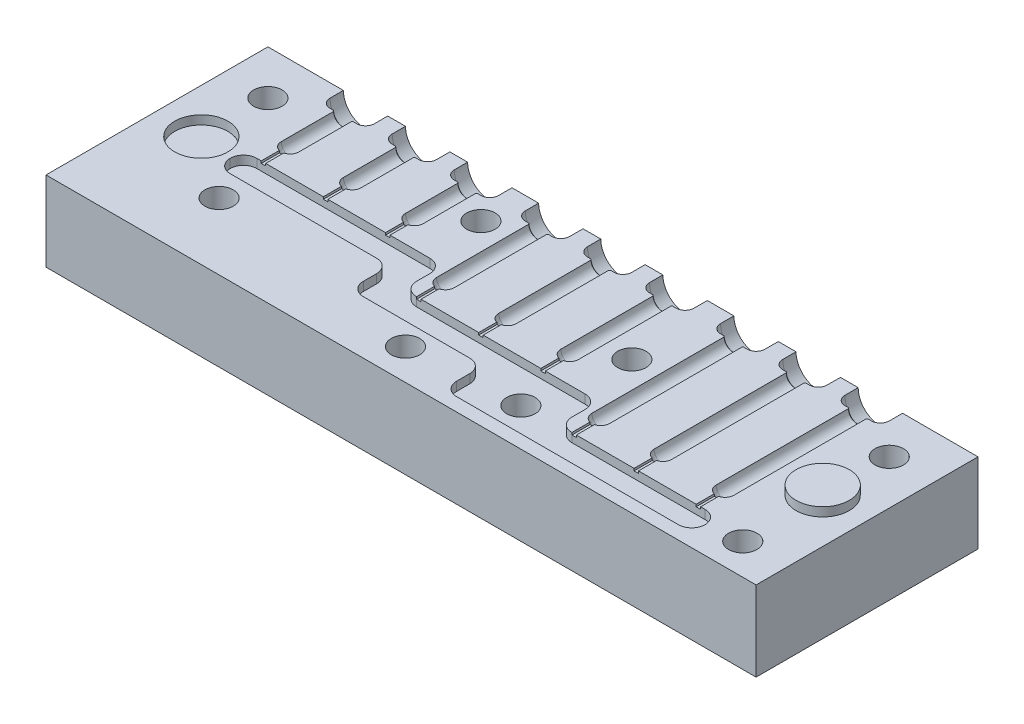
SolidWorks part; units mm, degrees
ref_plane "Ebene vorne" through (0, 0, 0) normal (0, 0, 1) x (1, 0, 0)
ref_plane "Ebene oben" through (0, 0, 0) normal (0, 1, 0) x (1, 0, 0)
ref_plane "Ebene rechts" through (0, 0, 0) normal (1, 0, 0) x (0, 0, -1)
sketch "Skizze1" plane through (0, 0, 0) normal (0, 1, 0) x (1, 0, 0)
  line L1 (0, 0) -> (80, 0)
  line L2 (0, 0) -> (0, 25)
  line L3 (0, 25) -> (80, 25)
  line L4 (80, 0) -> (80, 25)
  dimension "D1" = 80
  dimension "D2" = 25
extrude "Aufsatz-Linear austragen1" add sketch "Skizze1" along normal blind 9
sketch "Skizze2" plane through (0, 0, -25) normal (0, 0, -1) x (-1, 0, 0)
  line L0 (-80, 9) -> (0, 9) construction
  line L1 (-11, 9) -> (-18, 9) construction
  line L2 (-18, 9) -> (-25, 9) construction
  line L3 (-33, 9) -> (-40, 9) construction
  line L4 (-40, 9) -> (-47, 9) construction
  line L5 (-55, 9) -> (-62, 9) construction
  line L6 (-62, 9) -> (-69, 9) construction
  circle A0 centre (-11, 9) radius 1
  circle A1 centre (-18, 9) radius 1
  circle A2 centre (-25, 9) radius 1
  circle A3 centre (-33, 9) radius 1
  circle A4 centre (-40, 9) radius 1
  circle A5 centre (-47, 9) radius 1
  circle A6 centre (-55, 9) radius 1
  circle A7 centre (-62, 9) radius 1
  circle A8 centre (-69, 9) radius 1
  dimension "D1" = 2
  dimension "D2" = 7
  dimension "D3" = 11
  dimension "D5" = 8
  dimension "D4" = 3
extrude "Schnitt-Linear austragen1" cut sketch "Skizze2" against normal blind 9.5 contours A0 | A1 | A2
extrude "Schnitt-Linear austragen2" cut sketch "Skizze2<4>" against normal blind 14 contours A3 | A4 | A5
sketch "Skizze2<4>" plane through (0, 0, -25) normal (0, 0, -1) x (-1, 0, 0) same geometry as "Skizze2"
extrude "Schnitt-Linear austragen3" cut sketch "Skizze2<5>" against normal blind 18.5 contours A6 | A7 | A8
sketch "Skizze2<5>" plane through (0, 0, -25) normal (0, 0, -1) x (-1, 0, 0) same geometry as "Skizze2"
sketch "Skizze4" plane through (0, 0, -25) normal (0, 0, -1) x (-1, 0, 0)
  circle A0 centre (-11, 9) radius 2.5
  circle A1 centre (-18, 9) radius 2.5
  circle A2 centre (-25, 9) radius 2.5
  arc A3 (-12, 9) -> (-10, 9) centre (-11, 9) ccw construction
  arc A4 (-19, 9) -> (-17, 9) centre (-18, 9) ccw construction
  arc A5 (-26, 9) -> (-24, 9) centre (-25, 9) ccw construction
  circle A6 centre (-33, 9) radius 2.5
  circle A7 centre (-40, 9) radius 2.5
  circle A8 centre (-47, 9) radius 2.5
  circle A9 centre (-55, 9) radius 2.5
  circle A10 centre (-62, 9) radius 2.5
  circle A11 centre (-69, 9) radius 2.5
  dimension "D1" = 5
  dimension "D2" = 3
extrude "Schnitt-Linear austragen4" cut sketch "Skizze4" against normal blind 2.5
fillet "Verrundung1" radius 1 18 edges at (69, 6.5, -22.5) (62, 6.5, -22.5) (55, 6.5, -22.5) (47, 6.5, -22.5) (40, 6.5, -22.5) (33, 6.5, -22.5) (25, 6.5, -22.5) (18, 6.5, -22.5) (11, 6.5, -22.5) (11, 8, -15.5) (18, 8, -15.5) (25, 8, -15.5) (33, 8, -11) (40, 8, -11) (47, 8, -11) (55, 8, -6.5) (62, 8, -6.5) (69, 8, -6.5)
chamfer "Fase1" distance 0.1 angle 45 9 edges at (18, 8, -22.5) (11, 8, -22.5) (25, 8, -22.5) (47, 8, -22.5) (40, 8, -22.5) (33, 8, -22.5) (55, 8, -22.5) (62, 8, -22.5) (69, 8, -22.5)
sketch "Skizze5" plane through (0, 9, 0) normal (0, 1, 0) x (1, 0, 0)
  line L0 (11, 15.5) -> (11, 13.5) construction
  line L1 (33, 11) -> (33, 9) construction
  line L2 (10.75, 13.5) -> (11, 13.5)
  line L3 (10.75, 16.5) -> (10.75, 13.5)
  line L4 (11.25, 13.5) -> (11, 13.5)
  line L5 (32.75, 9) -> (33, 9)
  line L6 (32.75, 12) -> (32.75, 9)
  line L7 (33, 9) -> (33.25, 9)
  line L8 (10.75, 16.5) -> (11.25, 16.5)
  line L9 (55, 6.5) -> (55, 4.5) construction
  line L10 (17.75, 13.5) -> (18, 13.5)
  line L11 (33.25, 11) -> (33.25, 9) construction
  line L12 (32.75, 11) -> (32.75, 9) construction
  line L13 (32.75, 12) -> (33.25, 12)
  line L14 (54.75, 4.5) -> (55, 4.5)
  line L15 (54.75, 7.5) -> (54.75, 4.5)
  line L16 (55, 4.5) -> (55.25, 4.5)
  line L17 (54.75, 6.5) -> (54.75, 4.5) construction
  line L18 (11.25, 16.5) -> (11.25, 13.5)
  line L19 (33.25, 12) -> (33.25, 9)
  line L20 (17.75, 16.5) -> (17.75, 13.5)
  line L21 (18.25, 13.5) -> (18, 13.5)
  line L22 (55.25, 6.5) -> (55.25, 4.5) construction
  line L23 (54.75, 7.5) -> (55.25, 7.5)
  line L24 (55.25, 7.5) -> (55.25, 4.5)
  line L25 (39.75, 9) -> (40, 9)
  line L26 (39.75, 12) -> (39.75, 9)
  line L27 (11.25, 15.5) -> (11.25, 13.5) construction
  line L28 (10.75, 15.5) -> (10.75, 13.5) construction
  line L29 (17.75, 16.5) -> (18.25, 16.5)
  line L30 (18.25, 16.5) -> (18.25, 13.5)
  line L31 (18, 15.5) -> (18, 13.5) construction
  line L32 (24.75, 13.5) -> (25, 13.5)
  line L33 (24.75, 16.5) -> (24.75, 13.5)
  line L34 (25.25, 13.5) -> (25, 13.5)
  line L35 (24.75, 16.5) -> (25.25, 16.5)
  line L36 (25.25, 16.5) -> (25.25, 13.5)
  line L37 (25, 15.5) -> (25, 13.5) construction
  line L38 (40, 9) -> (40.25, 9)
  line L39 (39.75, 12) -> (40.25, 12)
  line L40 (40.25, 12) -> (40.25, 9)
  line L41 (40, 11) -> (40, 9) construction
  line L42 (46.75, 9) -> (47, 9)
  line L43 (46.75, 12) -> (46.75, 9)
  line L44 (47, 9) -> (47.25, 9)
  line L45 (46.75, 12) -> (47.25, 12)
  line L46 (47.25, 12) -> (47.25, 9)
  line L47 (47, 11) -> (47, 9) construction
  line L48 (61.75, 4.5) -> (62, 4.5)
  line L49 (61.75, 7.5) -> (61.75, 4.5)
  line L50 (62, 4.5) -> (62.25, 4.5)
  line L51 (61.75, 7.5) -> (62.25, 7.5)
  line L52 (62.25, 7.5) -> (62.25, 4.5)
  line L53 (62, 6.5) -> (62, 4.5) construction
  line L54 (68.75, 4.5) -> (69, 4.5)
  line L55 (68.75, 7.5) -> (68.75, 4.5)
  line L56 (69, 4.5) -> (69.25, 4.5)
  line L57 (68.75, 7.5) -> (69.25, 7.5)
  line L58 (69.25, 7.5) -> (69.25, 4.5)
  line L59 (69, 6.5) -> (69, 4.5) construction
  dimension "D1" = 2
  dimension "D2" = 0.5
  dimension "D4" = 7
  dimension "D5" = 3
  dimension "D6" = 7
  dimension "D8" = 7
  dimension "D3" = 3
  dimension "D7" = 3
extrude "Schnitt-Linear austragen5" cut sketch "Skizze5" against normal blind 0.25
sketch "Skizze6" plane through (0, 9, 0) normal (0, 1, 0) x (1, 0, 0)
  line L0 (31.25, 13.5) -> (8.75, 13.5)
  line L1 (31.25, 9) -> (53.25, 9)
  line L2 (31.25, 13.5) -> (31.25, 9)
  line L3 (25.25, 13.5) -> (25.25, 15.5318) construction
  line L4 (39.75, 9) -> (40.25, 9) construction
  line L5 (53.25, 9) -> (53.25, 4.5)
  line L6 (53.25, 4.5) -> (71.25, 4.5)
  line L7 (8.75, 13.5) -> (8.75, 10.5)
  line L8 (8.75, 10.5) -> (28.25, 10.5)
  line L9 (28.25, 10.5) -> (28.25, 6)
  line L10 (28.25, 6) -> (43.25, 6)
  line L11 (43.25, 6) -> (43.25, 1.5)
  line L12 (43.25, 1.5) -> (71.25, 1.5)
  line L13 (71.25, 1.5) -> (71.25, 4.5)
  line L14 (53.25, 4.5) -> (43.25, 4.5) construction
  line L15 (31.25, 9) -> (31.25, 6) construction
  line L16 (28.25, 10.5) -> (31.25, 10.5) construction
  line L17 (47.25, 9) -> (47.25, 11.0318) construction
  line L18 (68.75, 4.5) -> (69.25, 4.5) construction
  line L19 (10.75, 13.5) -> (11.25, 13.5) construction
  dimension "D1" = 6
  dimension "D2" = 3
  dimension "D3" = 6
  dimension "D4" = 10
  dimension "D5" = 2
  dimension "D6" = 2
extrude "Schnitt-Linear austragen6" cut sketch "Skizze6" against normal blind 1
sketch "Skizze7" plane through (0, 8, 0) normal (0, 1, 0) x (1, 0, 0)
  line L0 (43.25, 6) -> (53.25, 4.5) construction
  circle A0 centre (48.25, 5.25) radius 1.6
  dimension "D1" = 3.2
extrude "Schnitt-Linear austragen7" cut sketch "Skizze7" against normal up to next
hole_wizard "Durchgangsloch für M31" positions "Skizze9" profile "Skizze8" hole size "M3" standard "DIN" end condition through all
sketch "Skizze9" plane through (0, 9, 0) normal (0, 1, 0) x (1, 0, 0)
  line L0 (0, 25) -> (0, 0) construction
  line L1 (8.5, 25) -> (0, 25) construction
  line L2 (5, 20) -> (29, 20)
  line L5 (29, 20) -> (75, 20)
  line L7 (80, 0) -> (80, 25) construction
  line L8 (75, 3.5) -> (37, 3.5)
  line L9 (37, 3.5) -> (12, 3.5)
  line L10 (12, 3.5) -> (12, 7.5)
  line L12 (0, 0) -> (80, 0) construction
  point P0 (29, 20)
  point P2 (51, 15)
  point P4 (75, 20)
  point P6 (75, 3.5)
  point P8 (12, 7.5)
  point P10 (5, 20)
  point P34 (37, 3.5)
  dimension "D1" = 5
  dimension "D2" = 5
  dimension "D3" = 29
  dimension "D4" = 5
  dimension "D5" = 29
  dimension "D6" = 5
  dimension "D7" = 12
  dimension "D8" = 5
  dimension "D9" = 3.5
  dimension "D10" = 4
  dimension "D11" = 25
sketch "Skizze8" plane through (29, 9, -20) normal (1, 0, 0) x (0, 0, 1)
  line L0 (0, 0) -> (0, 9)
  line L1 (0, 9) -> (1.6, 9)
  line L2 (1.6, 9) -> (1.6, 0)
  line L5 (1.6, 0) -> (0, 0)
  line L11 (0, -6.35) -> (0, 107.95) construction
  dimension "Bohrerdurchmesser" = 3.2
  dimension "Bohrungstiefe" = 9
sketch "Skizze10" plane through (0, 9, 0) normal (0, 1, 0) x (1, 0, 0)
  line L0 (0, 12.5) -> (5, 12.5) construction
  line L1 (0, 25) -> (0, 0) construction
  line L2 (5, 12.5) -> (75, 12.5) construction
  line L3 (75, 12.5) -> (80, 12.5) construction
  line L4 (80, 0) -> (80, 25) construction
  circle A0 centre (5, 12.5) radius 3
  circle A1 centre (75, 12.5) radius 3
  dimension "D1" = 6
  dimension "D2" = 5
extrude "Schnitt-Linear austragen8" cut sketch "Skizze10" against normal blind 1 contours A0
extrude "Aufsatz-Linear austragen2" add sketch "Skizze10<3>" along normal blind 1 contours A1 region at (75, 9, -12.5)
sketch "Skizze10<3>" plane through (0, 9, 0) normal (0, 1, 0) x (1, 0, 0) same geometry as "Skizze10"
fillet "Verrundung2" radius 1.5 12 edges at (71.25, 8.5, -1.5) (71.25, 8.5, -4.5) (53.25, 8.5, -4.5) (53.25, 8.5, -9) (43.25, 8.5, -1.5) (43.25, 8.5, -6) (28.25, 8.5, -10.5) (31.25, 8.5, -13.5) (28.25, 8.5, -6) (31.25, 8.5, -9) (8.75, 8.5, -10.5) (8.75, 8.5, -13.5)
